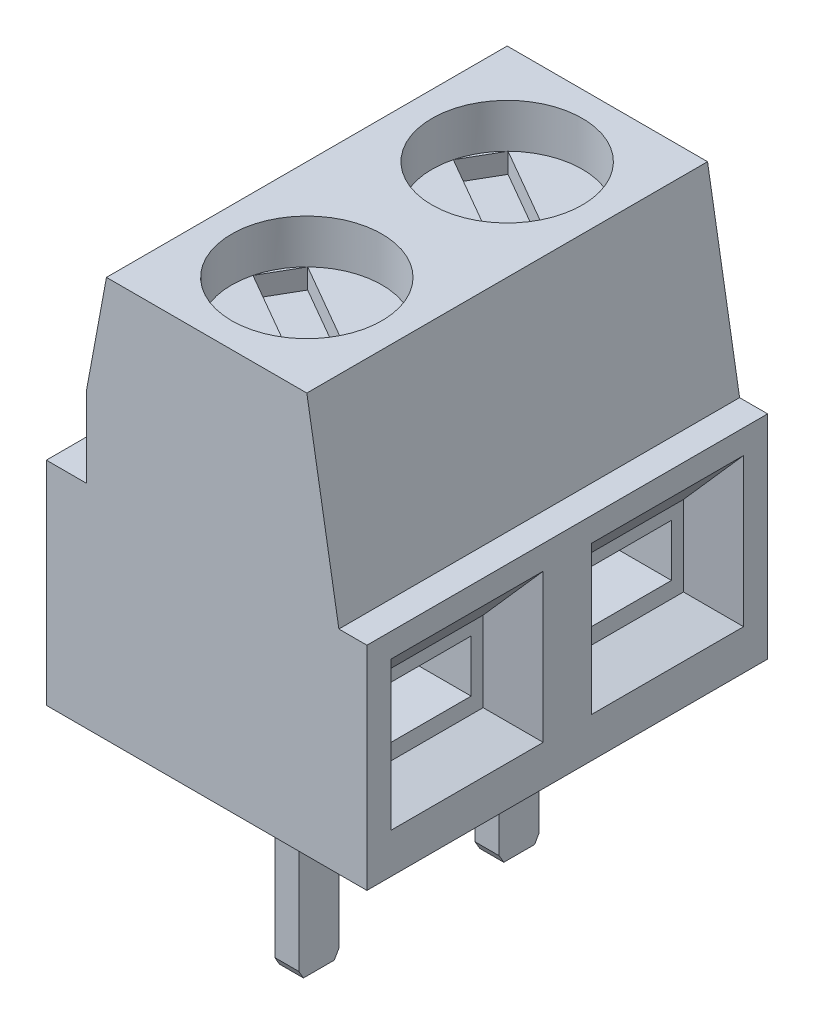
SolidWorks part; units mm, degrees
ref_plane "X Y" through (0, 0, 0) normal (0, 0, 1) x (1, 0, 0)
ref_plane "X -Z" through (0, 0, 0) normal (0, 1, 0) x (1, 0, 0)
ref_plane "-Z Y" through (0, 0, 0) normal (1, 0, 0) x (0, 0, -1)
sketch "Skica1" plane through (0, 0, 0) normal (0, 0, 1) x (1, 0, 0)
  line L0 (-2.5, 10) -> (2.5, 10)
  line L1 (2.5, 10) -> (3.3, 5.3)
  line L2 (3.3, 5.3) -> (4, 5.3)
  line L3 (4, 5.3) -> (4, 0)
  line L4 (4, 0) -> (-4, 0)
  line L5 (-4, 0) -> (-4, 5.3)
  line L6 (-4, 5.3) -> (-3, 5.3)
  line L7 (-3, 5.3) -> (-3, 7.3)
  line L8 (-3, 7.3) -> (-2.5, 10)
  dimension "D1" = 10
  dimension "D2" = 0.7
  dimension "D3" = 1
  dimension "D4" = 8
  dimension "D5" = 5.3
  dimension "D6" = 5.3
  dimension "D7" = 2
  dimension "D8" = 1.5
  dimension "D9" = 5
extrude "Základ-Protažení" add sketch "Skica1" along normal blind 10
sketch "Skica2" plane through (0, 10, 0) normal (0, 1, 0) x (-1, 0, 0)
  line L0 (-2.5, 0) -> (2.5, 0) construction
  line L1 (2.5, 10) -> (2.5, 0) construction
  circle A0 centre (0, 2.5) radius 1.875
  circle A1 centre (0, 7.5) radius 1.875
  dimension "D1" = 3.75
  dimension "D2" = 2.5
  dimension "D3" = 2.5
  dimension "D4" = 5
extrude "Odebrání-Protažení1" cut sketch "Skica2" against normal blind 1.1
sketch "Skica3" plane through (0, 8.9, 0) normal (0, 1, 0) x (-1, 0, 0)
  line L0 (1.815, 2.0295) -> (-1.315, 3.8366)
  line L1 (1.815, 2.0295) -> (1.315, 1.1634)
  line L2 (-1.315, 3.8366) -> (-1.815, 2.9705)
  line L3 (1.315, 1.1634) -> (-1.815, 2.9705)
  line L4 (-2.5, 0) -> (2.5, 0) construction
  line L5 (-1.315, 8.8366) -> (1.815, 7.0295)
  line L6 (-1.315, 8.8366) -> (-1.815, 7.9705)
  line L7 (-1.815, 7.9705) -> (1.315, 6.1634)
  line L8 (1.815, 7.0295) -> (1.315, 6.1634)
  circle A0 centre (0, 2.5) radius 1.875 construction
  dimension "D1" = 1
  dimension "D2" = 30
  dimension "D3" = 5
extrude "Odebrání-Protažení2" cut sketch "Skica3" against normal blind 0.5
sketch "Skica4" plane through (-4, 0, 0) normal (-1, 0, 0) x (0, 0, 1)
  line L0 (10, 5.3) -> (0, 5.3) construction
  line L1 (8.55, 5.3) -> (6.45, 5.3)
  line L2 (8.55, 5.3) -> (8.55, 2.3)
  line L3 (8.55, 2.3) -> (6.45, 2.3)
  line L4 (6.45, 5.3) -> (6.45, 2.3)
  line L5 (10, 0) -> (0, 0) construction
  line L6 (8.1, 0) -> (6.9, 0)
  line L7 (8.1, 0) -> (8.1, 1)
  line L8 (8.1, 1) -> (6.9, 1)
  line L9 (6.9, 0) -> (6.9, 1)
  line L10 (10, 5.3) -> (10, 0) construction
  line L11 (3.55, 5.3) -> (1.45, 5.3)
  line L12 (3.55, 5.3) -> (3.55, 2.3)
  line L13 (3.55, 2.3) -> (1.45, 2.3)
  line L14 (1.45, 5.3) -> (1.45, 2.3)
  line L15 (3.1, 0) -> (1.9, 0)
  line L16 (3.1, 0) -> (3.1, 1)
  line L17 (3.1, 1) -> (1.9, 1)
  line L18 (1.9, 0) -> (1.9, 1)
  line L19 (-1.45, 5.3) -> (-3.55, 5.3)
  line L20 (-1.45, 5.3) -> (-1.45, 2.3)
  line L21 (-1.45, 2.3) -> (-3.55, 2.3)
  line L22 (-3.55, 5.3) -> (-3.55, 2.3)
  line L23 (-1.9, 0) -> (-3.1, 0)
  line L24 (-1.9, 0) -> (-1.9, 1)
  line L25 (-1.9, 1) -> (-3.1, 1)
  line L26 (-3.1, 0) -> (-3.1, 1)
  line L27 (10, 10) -> (0, 10) construction
  dimension "D1" = 2.1
  dimension "D2" = 1.45
  dimension "D3" = 3
  dimension "D4" = 1.2
  dimension "D5" = 0.45
  dimension "D6" = 1
  dimension "D7" = 2.9
  dimension "D8" = 4.7
extrude "Odebrání-Protažení3" cut sketch "Skica4" against normal blind 0.5
sketch "Skica5" plane through (4, 0, 0) normal (1, 0, 0) x (0, 0, -1)
  line L0 (-10, 0) -> (0, 0) construction
  line L1 (-8.9, 3.5) -> (-6.1, 3.5)
  line L2 (-8.9, 3.5) -> (-8.9, 1.5)
  line L3 (-8.9, 1.5) -> (-6.1, 1.5)
  line L4 (-6.1, 3.5) -> (-6.1, 1.5)
  line L5 (-10, 0) -> (-10, 5.3) construction
  dimension "D1" = 2.8
  dimension "D2" = 2
  dimension "D3" = 1.5
  dimension "D4" = 1.1
extrude "Odebrání-Protažení4" cut sketch "Skica5" against normal blind 1
pattern_linear "Lineární Pole1" count 3 spacing 5 along (0, 0, -1) of "Odebrání-Protažení4"
chamfer "Zkosení1" distance 1.2 distance2 1 2 edges at (4, 3.5, 7.5) (4, 3.5, 2.5) first distance on face at (4, 2.5, 2.5)
chamfer "Zkosení2" distance 0.5 distance2 1 6 edges at (4, 3.1, 6.1) (4, 1.5, 7.5) (4, 3.1, 8.9) (4, 3.1, 1.1) (4, 1.5, 2.5) (4, 3.1, 3.9) first distance on face at (4, 3.1, 2.5)
sketch "Skica6" plane through (3, 0, 0) normal (1, 0, 0) x (0, 0, -1)
  line L0 (-6.1, 3.5) -> (-8.9, 3.5) construction
  line L1 (-8.5, 3.2) -> (-6.4, 3.2)
  line L2 (-8.5, 3.2) -> (-8.5, 1.9)
  line L3 (-8.5, 1.9) -> (-6.4, 1.9)
  line L4 (-6.4, 3.2) -> (-6.4, 1.9)
  line L6 (-6.1, 1.5) -> (-6.1, 3.5) construction
  dimension "D1" = 1.3
  dimension "D2" = 2.1
  dimension "D4" = 0.3
  dimension "D6" = 0.3
extrude "Odebrání-Protažení5" cut sketch "Skica6" against normal blind 2
pattern_linear "Lineární Pole2" count 3 spacing 5 along (0, 0, -1) of "Odebrání-Protažení5"
sketch "Skica7" plane through (0, 0, 0) normal (0, -1, 0) x (1, 0, 0)
  line L0 (-4, 0) -> (4, 0) construction
  line L1 (-0.3, 2) -> (0.3, 2)
  line L2 (-0.3, 2) -> (-0.3, 3)
  line L3 (-0.3, 3) -> (0.3, 3)
  line L4 (0.3, 2) -> (0.3, 3)
  line L5 (-4, 1.9) -> (-4, 0) construction
  dimension "D1" = 0.6
  dimension "D2" = 1
  dimension "D3" = 2
  dimension "D4" = 3.7
extrude "Přidání-Protažení1" add sketch "Skica7" along normal blind 4.8
pattern_linear "Lineární Pole3" count 2 spacing 5 along (0, 0, 1) of "Přidání-Protažení1"
chamfer "Zkosení3" distance 0.2 angle 30 4 edges at (0, -4.8, 3) (0, -4.8, 2) (0, -4.8, 8) (0, -4.8, 7) first distance on face at (0, -2.4, 3) first distance on face at (0, -2.4, 2) first distance on face at (0, -2.4, 8) first distance on face at (0, -2.4, 7)
sketch "Sketch1" plane through (0, 0, 0) normal (0, -1, 0) x (1, 0, 0)
  line L0 (-0.3, 7.5) -> (0.3, 7.5) construction
  line L1 (-0.3, 7.8845) -> (-0.3, 7.1155) construction
  line L2 (0.3, 7.1155) -> (0.3, 7.8845) construction
  line L3 (-0.3, 2.5) -> (0.3, 2.5) construction
  line L4 (-0.3, 3) -> (-0.3, 2) construction
  line L5 (0.3, 2) -> (0.3, 3) construction
  circle A0 centre (0, 7.5) radius 0.7131
  circle A1 centre (0, 2.5) radius 0.7131
  dimension "D1" = 1.4261
